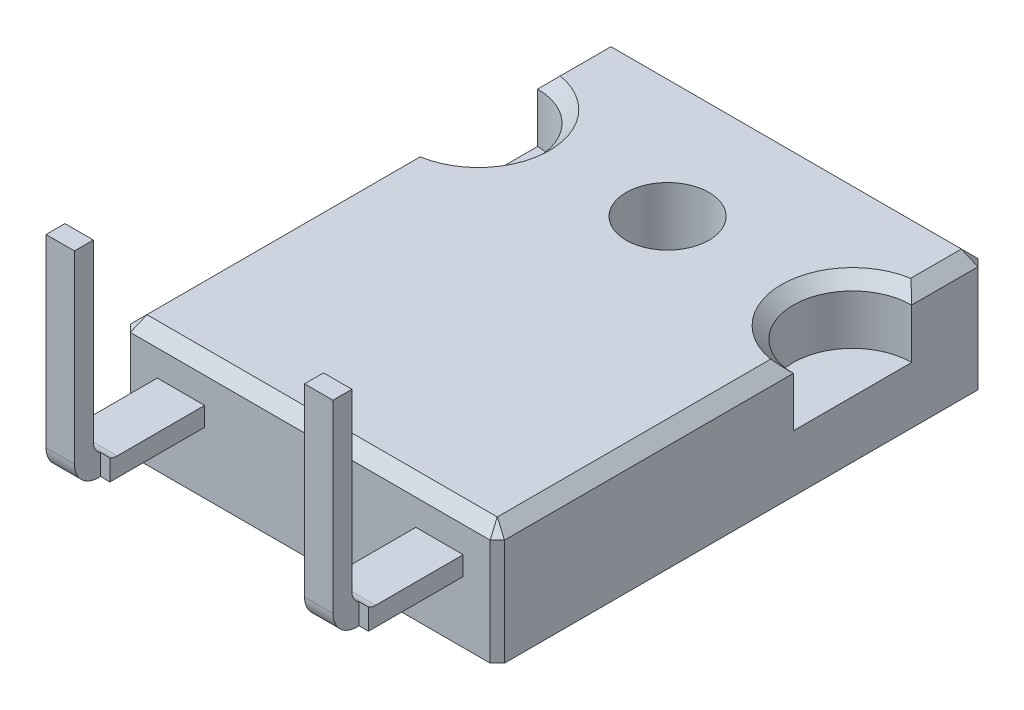
SolidWorks part; units mm, degrees
ref_plane "Спереди" through (0, 0, 0) normal (0, 0, 1) x (1, 0, 0)
ref_plane "Сверху" through (0, 0, 0) normal (0, 1, 0) x (1, 0, 0)
ref_plane "Справа" through (0, 0, 0) normal (1, 0, 0) x (0, 0, -1)
sketch "Эскиз1" plane through (0, 0, 0) normal (0, 1, 0) x (1, 0, 0)
  line L0 (0, 4.79) -> (0, -49995.21) construction
  line L1 (7.9, -10.3) -> (-7.9, -10.3)
  line L2 (7.9, -10.3) -> (7.9, 10.3)
  line L3 (7.9, 10.3) -> (-7.9, 10.3)
  line L4 (-7.9, -10.3) -> (-7.9, 10.3)
  line L5 (7.9, -10.3) -> (-7.9, 10.3) construction
  line L6 (7.9, 10.3) -> (-7.9, -10.3) construction
  line L7 (-5.46, 4.79) -> (-5.46, -49995.21) construction
  line L8 (5.46, 4.79) -> (5.46, -49995.21) construction
  line L9 (-6.46, 4.79) -> (-6.46, -49995.21) construction
  line L10 (-4.46, 4.79) -> (-4.46, -49995.21) construction
  line L11 (6.46, -10.3) -> (6.46, -14.3)
  line L12 (-6.46, -10.3) -> (-4.46, -10.3)
  line L13 (-6.46, -10.3) -> (-6.46, -14.3)
  line L14 (-6.46, -14.3) -> (-4.46, -14.3)
  line L15 (-4.46, -10.3) -> (-4.46, -14.3)
  line L16 (-6.46, -10.3) -> (-4.46, -14.3) construction
  line L17 (-6.46, -14.3) -> (-4.46, -10.3) construction
  line L18 (6.46, -14.3) -> (4.46, -14.3)
  line L19 (4.46, -10.3) -> (4.46, -14.3)
  line L20 (-6.06, 4.79) -> (-6.06, -49995.21) construction
  line L21 (-4.86, 4.79) -> (-4.86, -49995.21) construction
  line L22 (4.86, -14.3) -> (4.86, -15.4)
  line L23 (-6.06, -14.3) -> (-4.86, -14.3)
  line L24 (-6.06, -14.3) -> (-6.06, -15.4)
  line L25 (-6.06, -15.4) -> (-4.86, -15.4)
  line L26 (-4.86, -14.3) -> (-4.86, -15.4)
  line L27 (-6.06, -14.3) -> (-4.86, -15.4) construction
  line L28 (-6.06, -15.4) -> (-4.86, -14.3) construction
  line L29 (6.06, -15.4) -> (4.86, -15.4)
  line L30 (6.06, -14.3) -> (6.06, -15.4)
  line L31 (-6.06, -14.6) -> (-4.86, -14.6)
  line L32 (6.06, -14.6) -> (4.86, -14.6)
  circle A0 centre (0, 4.79) radius 1.75
  arc A1 (-7.9, 2.2) -> (-7.9, 7.2) centre (-7.9, 4.7) ccw
  arc A2 (7.9, 2.2) -> (7.9, 7.2) centre (7.9, 4.7) cw
  point P0 (0, 0)
  point P25 (-5.46, -12.3)
  point P38 (-5.46, -14.85)
  dimension "D3" = 3.5
  dimension "D6" = 5.6
  dimension "D7" = 5
  dimension "D1" = 15.8
  dimension "D2" = 20.6
  dimension "D4" = 7.9
  dimension "D5" = 5.51
  dimension "D8" = 5.46
  dimension "D9" = 5.46
  dimension "D12" = 4
  dimension "D15" = 1.1
  dimension "D16" = 0.8
  dimension "D10" = 1
  dimension "D11" = 1
  dimension "D13" = 0.6
  dimension "D14" = 0.6
extrude "Бобышка-Вытянуть1" add sketch "Эскиз1" along normal blind 2.6 contours L2 A2 L3 L4 A1 L1 A0 region at (0, 0, 0.4671)
extrude "Бобышка-Вытянуть2" add sketch "Эскиз1<3>" against normal blind 2.4 contours L2 A2 L3 L4 A1 L1 A0 | A2 L2 | L4 A1 region at (0, 0, 0.4671) region at (6.839, 0, -4.7) region at (-6.839, 0, -4.7)
sketch "Эскиз1<3>" plane through (0, 0, 0) normal (0, 1, 0) x (1, 0, 0) same geometry as "Эскиз1"
extrude "Бобышка-Вытянуть3" add sketch "Эскиз1<4>" along normal blind 0.8 from offset 0.2 separate body contours L15 L1 L13 L14 | L24 L31 L26 L14 | L31 L24 L25 L26 | L1 L19 L18 L11 | L32 L30 L18 L22 | L30 L32 L22 L29 region at (5.46, 0, 12.3) region at (-5.46, 0, 12.3) region at (5.46, 0, 14.45) region at (5.46, 0, 15) region at (-5.46, 0, 14.45) region at (-5.46, 0, 15)
sketch "Эскиз1<4>" plane through (0, 0, 0) normal (0, 1, 0) x (1, 0, 0) same geometry as "Эскиз1"
extrude "Бобышка-Вытянуть4" add sketch "Эскиз1<5>" along normal blind 8.8 from offset 0.2 contours L31 L24 L25 L26 | L30 L32 L22 L29 region at (5.46, 0, 15) region at (-5.46, 0, 15)
sketch "Эскиз1<5>" plane through (0, 0, 0) normal (0, 1, 0) x (1, 0, 0) same geometry as "Эскиз1"
fillet "Скругление1" radius 1 1 edges at (-5.46, 0.2, 15.4)
fillet "Скругление2" radius 1 1 edges at (5.46, 0.2, 15.4)
fillet "Скругление3" radius 0.6 1 edges at (-5.46, 1, 14.6)
fillet "Скругление4" radius 0.6 1 edges at (5.46, 1, 14.6)
chamfer "Фаска1" distance 0.3 angle 45 4 edges at (-7.9, 0.1, 10.3) (-7.9, 0.1, -10.3) (7.9, 0.1, -10.3) (7.9, 0.1, 10.3)
chamfer "Фаска2" distance 0.5 angle 45 12 edges at (-5.4, 2.6, -4.7) (-7.9, 2.6, -8.6) (-7.75, 2.6, -10.15) (0, 2.6, -10.3) (7.75, 2.6, -10.15) (7.9, 2.6, -8.6) (5.4, 2.6, -4.7) (7.9, 2.6, 3.9) (7.75, 2.6, 10.15) (0, 2.6, 10.3) (-7.75, 2.6, 10.15) (-7.9, 2.6, 3.9)
sketch "Эскиз2" plane through (0, -2.4, 0) normal (0, -1, 0) x (1, 0, 0)
  line L0 (-6.9, -9.3) -> (6.9, -9.3)
  line L1 (6.9, -9.3) -> (6.9, -9.3)
  line L2 (6.9, -9.3) -> (6.9, 9.3)
  line L3 (6.9, 9.3) -> (6.9, 9.3)
  line L4 (6.9, 9.3) -> (-6.9, 9.3)
  line L5 (-6.9, 9.3) -> (-6.9, 9.3)
  line L6 (-6.9, 9.3) -> (-6.9, -9.3)
  line L7 (-6.9, -9.3) -> (-6.9, -9.3)
  line L8 (7.6, 10.3) -> (-7.6, 10.3)
  line L9 (-7.6, 10.3) -> (-7.9, 10)
  line L10 (-7.9, 10) -> (-7.9, -10)
  line L11 (-7.9, -10) -> (-7.6, -10.3)
  line L12 (-7.6, -10.3) -> (7.6, -10.3)
  line L13 (7.6, -10.3) -> (7.9, -10)
  line L14 (7.9, -10) -> (7.9, 10)
  line L15 (7.9, 10) -> (7.6, 10.3)
  line L16 (7.6, 10.3) -> (-7.6, 10.3)
  line L17 (-7.6, 10.3) -> (-7.9, 10)
  line L18 (-7.9, 10) -> (-7.9, -10)
  line L19 (-7.9, -10) -> (-7.6, -10.3)
  line L20 (-7.6, -10.3) -> (7.6, -10.3)
  line L21 (7.6, -10.3) -> (7.9, -10)
  line L22 (7.9, -10) -> (7.9, 10)
  line L23 (7.9, 10) -> (7.6, 10.3)
  circle M9 centre (0, -4.79) radius 1.75
  dimension "D1" = 0
  dimension "D2" = 1
extrude "Вырез-Вытянуть1" cut sketch "Эскиз2" against normal blind 1.5 contours L4 L6 L0 L2 M9 region at (0, -2.4, 0.1865)
extrude "Бобышка-Вытянуть5" add sketch "Эскиз2<3>" along normal blind 1.5 from surface separate body contours L4 L6 L0 L2 M9 region at (0, -2.4, 0.1865) starting at face at (0, -0.9, -6.54)
sketch "Эскиз2<3>" plane through (0, -2.4, 0) normal (0, -1, 0) x (1, 0, 0) same geometry as "Эскиз2"
